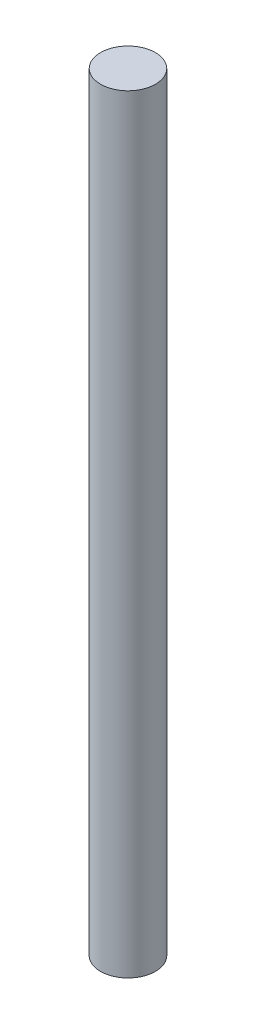
SolidWorks part; units mm, degrees
ref_plane "Спереди" through (0, 0, 0) normal (0, 0, 1) x (1, 0, 0)
ref_plane "Сверху" through (0, 0, 0) normal (0, 1, 0) x (1, 0, 0)
ref_plane "Справа" through (0, 0, 0) normal (1, 0, 0) x (0, 0, -1)
sketch "Эскиз1" plane through (0, 0, 0) normal (0, 1, 0) x (1, 0, 0)
  circle A0 centre (0, 0) radius 2.5
  dimension "D1" = 5
extrude "Вытянуть1" add sketch "Эскиз1" along normal blind 70
